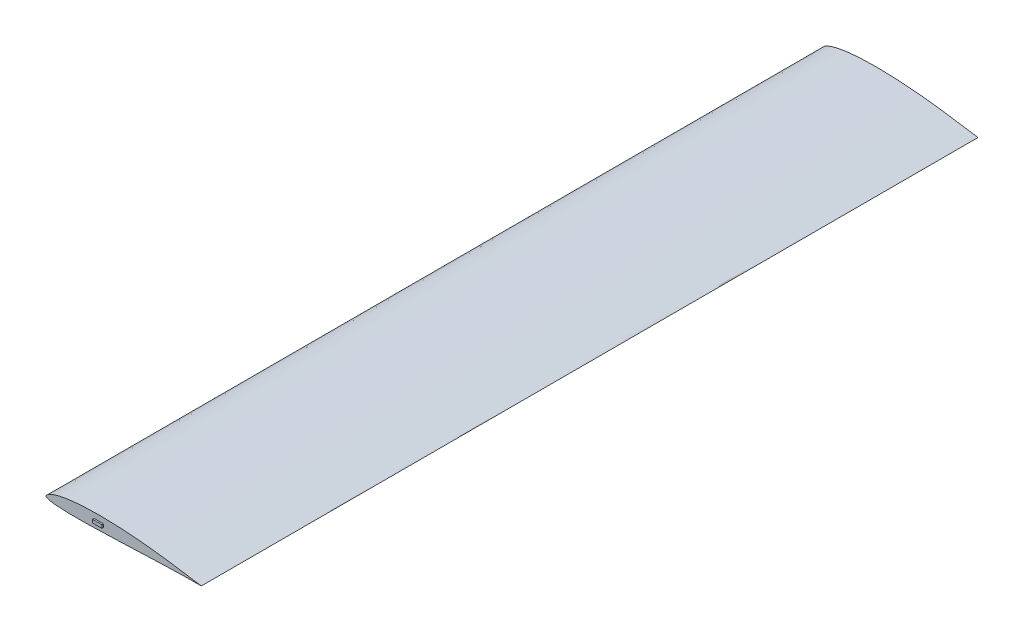
SolidWorks part; units mm, degrees
material "EPP"
ref_plane "Front Plane" through (0, 0, 0) normal (0, 0, 1) x (1, 0, 0)
ref_plane "Top Plane" through (0, 0, 0) normal (0, 1, 0) x (1, 0, 0)
ref_plane "Right Plane" through (0, 0, 0) normal (1, 0, 0) x (0, 0, -1)
curve "Curve1"
  spline degree 3 poles (49.6515, 0.009, 0) (50.0884, -0.0053, 0) (49.6522, 0.033, 0) (49.3011, 0.0832, 0) (48.4593, 0.1945, 0) (47.4415, 0.3499, 0) (46.1338, 0.5549, 0) (44.6155, 0.7993, 0) (42.8923, 1.0751, 0) (40.9958, 1.371, 0) (38.9477, 1.6747, 0) (36.7703, 1.9711, 0) (34.4838, 2.2498, 0) (32.109, 2.5048, 0) (29.6686, 2.7322, 0) (27.1889, 2.9318, 0) (24.6971, 3.0996, 0) (22.2188, 3.2252, 0) (19.7784, 3.3048, 0) (17.3996, 3.3388, 0) (15.1043, 3.321, 0) (12.9138, 3.2492, 0) (10.8475, 3.1296, 0) (8.9245, 2.9596, 0) (7.1613, 2.7404, 0) (5.5715, 2.4767, 0) (4.1671, 2.1739, 0) (2.9576, 1.8376, 0) (1.9505, 1.4773, 0) (1.1488, 1.103, 0) (0.5587, 0.7311, 0) (0.2281, 0.4366, 0) (0.09, 0.2394, 0) (0.0408, 0.1522, 0) (0.0104, 0.0738, 0) (-0.0015, 0.012, 0) (0.0009, -0.0367, 0) (0.0247, -0.0804, 0) (0.0694, -0.1305, 0) (0.1411, -0.1885, 0) (0.3144, -0.2962, 0) (0.7005, -0.4536, 0) (1.3781, -0.6282, 0) (2.3375, -0.7877, 0) (3.539, -0.9182, 0) (4.9742, -1.0154, 0) (6.6312, -1.0793, 0) (8.4956, -1.1107, 0) (10.5497, -1.112, 0) (12.7728, -1.0868, 0) (15.1414, -1.0389, 0) (17.6298, -0.9723, 0) (20.2103, -0.8906, 0) (22.8538, -0.7976, 0) (25.5303, -0.6969, 0) (28.2091, -0.5925, 0) (30.859, -0.4876, 0) (33.449, -0.3866, 0) (35.9478, -0.2924, 0) (38.325, -0.208, 0) (40.551, -0.1358, 0) (42.5964, -0.0785, 0) (44.4361, -0.0365, 0) (46.0378, -0.0091, 0) (47.399, 0.0043, 0) (48.4441, 0.0096, 0) (49.2972, 0.0042, 0) (49.6515, 0.009, 0) (50.0884, -0.0053, 0) (49.6522, 0.033, 0) knots -0.014204 -0.006419 -0.001632 0 0.001631 0.006435 0.014221 0.024766 0.037827 0.053149 0.070474 0.089536 0.110075 0.13186 0.154693 0.178371 0.20268 0.227364 0.252133 0.276728 0.300939 0.324527 0.347267 0.368992 0.389507 0.408628 0.426224 0.442179 0.456396 0.468805 0.479372 0.488086 0.494968 0.500034 0.501036 0.502094 0.502997 0.503513 0.503956 0.504409 0.504955 0.505943 0.50713 0.510998 0.518232 0.527846 0.539809 0.554056 0.57049 0.588974 0.609342 0.631393 0.654894 0.67959 0.705203 0.731447 0.75802 0.78462 0.810936 0.836657 0.861473 0.885081 0.907188 0.927507 0.945765 0.961712 0.975122 0.985796 0.993581 0.998368 1 1.001631 1.006435 1.014221 periodic
sketch "Sketch1" plane through (0, 0, 0) normal (0, 0, 1) x (1, 0, 0)
  spline S0 degree 3 poles (49.6515, 0.009) (50.0884, -0.0053) (49.6522, 0.033) (49.3011, 0.0832) (48.4593, 0.1945) (47.4415, 0.3499) (46.1338, 0.5549) (44.6155, 0.7993) (42.8923, 1.0751) (40.9958, 1.371) (38.9477, 1.6747) (36.7703, 1.9711) (34.4838, 2.2498) (32.109, 2.5048) (29.6686, 2.7322) (27.1889, 2.9318) (24.6971, 3.0996) (22.2188, 3.2252) (19.7784, 3.3048) (17.3996, 3.3388) (15.1043, 3.321) (12.9138, 3.2492) (10.8475, 3.1296) (8.9245, 2.9596) (7.1613, 2.7404) (5.5715, 2.4767) (4.1671, 2.1739) (2.9576, 1.8376) (1.9505, 1.4773) (1.1488, 1.103) (0.5587, 0.7311) (0.2281, 0.4366) (0.09, 0.2394) (0.0408, 0.1522) (0.0104, 0.0738) (-0.0015, 0.012) (0.0009, -0.0367) (0.0247, -0.0804) (0.0694, -0.1305) (0.1411, -0.1885) (0.3144, -0.2962) (0.7005, -0.4536) (1.3781, -0.6282) (2.3375, -0.7877) (3.539, -0.9182) (4.9742, -1.0154) (6.6312, -1.0793) (8.4956, -1.1107) (10.5497, -1.112) (12.7728, -1.0868) (15.1414, -1.0389) (17.6298, -0.9723) (20.2103, -0.8906) (22.8538, -0.7976) (25.5303, -0.6969) (28.2091, -0.5925) (30.859, -0.4876) (33.449, -0.3866) (35.9478, -0.2924) (38.325, -0.208) (40.551, -0.1358) (42.5964, -0.0785) (44.4361, -0.0365) (46.0378, -0.0091) (47.399, 0.0043) (48.4441, 0.0096) (49.2972, 0.0042) (49.6515, 0.009) (50.0884, -0.0053) (49.6522, 0.033) knots -0.014204 -0.006419 -0.001632 0 0.001631 0.006435 0.014221 0.024766 0.037827 0.053149 0.070474 0.089536 0.110075 0.13186 0.154693 0.178371 0.20268 0.227364 0.252133 0.276728 0.300939 0.324527 0.347267 0.368992 0.389507 0.408628 0.426224 0.442179 0.456396 0.468805 0.479372 0.488086 0.494968 0.500034 0.501036 0.502094 0.502997 0.503513 0.503956 0.504409 0.504955 0.505943 0.50713 0.510998 0.518232 0.527846 0.539809 0.554056 0.57049 0.588974 0.609342 0.631393 0.654894 0.67959 0.705203 0.731447 0.75802 0.78462 0.810936 0.836657 0.861473 0.885081 0.907188 0.927507 0.945765 0.961712 0.975122 0.985796 0.993581 0.998368 1 1.001631 1.006435 1.014221 only from (50, 0) to (50, 0) construction
  spline S1 degree 3 poles (49.6515, 0.009) (50.0884, -0.0053) (49.6522, 0.033) (49.3011, 0.0832) (48.4593, 0.1945) (47.4415, 0.3499) (46.1338, 0.5549) (44.6155, 0.7993) (42.8923, 1.0751) (40.9958, 1.371) (38.9477, 1.6747) (36.7703, 1.9711) (34.4838, 2.2498) (32.109, 2.5048) (29.6686, 2.7322) (27.1889, 2.9318) (24.6971, 3.0996) (22.2188, 3.2252) (19.7784, 3.3048) (17.3996, 3.3388) (15.1043, 3.321) (12.9138, 3.2492) (10.8475, 3.1296) (8.9245, 2.9596) (7.1613, 2.7404) (5.5715, 2.4767) (4.1671, 2.1739) (2.9576, 1.8376) (1.9505, 1.4773) (1.1488, 1.103) (0.5587, 0.7311) (0.2281, 0.4366) (0.09, 0.2394) (0.0408, 0.1522) (0.0104, 0.0738) (-0.0015, 0.012) (0.0009, -0.0367) (0.0247, -0.0804) (0.0694, -0.1305) (0.1411, -0.1885) (0.3144, -0.2962) (0.7005, -0.4536) (1.3781, -0.6282) (2.3375, -0.7877) (3.539, -0.9182) (4.9742, -1.0154) (6.6312, -1.0793) (8.4956, -1.1107) (10.5497, -1.112) (12.7728, -1.0868) (15.1414, -1.0389) (17.6298, -0.9723) (20.2103, -0.8906) (22.8538, -0.7976) (25.5303, -0.6969) (28.2091, -0.5925) (30.859, -0.4876) (33.449, -0.3866) (35.9478, -0.2924) (38.325, -0.208) (40.551, -0.1358) (42.5964, -0.0785) (44.4361, -0.0365) (46.0378, -0.0091) (47.399, 0.0043) (48.4441, 0.0096) (49.2972, 0.0042) (49.6515, 0.009) (50.0884, -0.0053) (49.6522, 0.033) knots -0.014204 -0.006419 -0.001632 0 0.001631 0.006435 0.014221 0.024766 0.037827 0.053149 0.070474 0.089536 0.110075 0.13186 0.154693 0.178371 0.20268 0.227364 0.252133 0.276728 0.300939 0.324527 0.347267 0.368992 0.389507 0.408628 0.426224 0.442179 0.456396 0.468805 0.479372 0.488086 0.494968 0.500034 0.501036 0.502094 0.502997 0.503513 0.503956 0.504409 0.504955 0.505943 0.50713 0.510998 0.518232 0.527846 0.539809 0.554056 0.57049 0.588974 0.609342 0.631393 0.654894 0.67959 0.705203 0.731447 0.75802 0.78462 0.810936 0.836657 0.861473 0.885081 0.907188 0.927507 0.945765 0.961712 0.975122 0.985796 0.993581 0.998368 1 1.001631 1.006435 1.014221 only from (50, 0) to (50, 0)
extrude "Boss-Extrude1" add sketch "Sketch1" along normal blind 250
sketch "Sketch2" plane through (0, 0, 250) normal (0, 0, 1) x (1, 0, 0)
  line L0 (0, 0) -> (50, 0) construction
  line L1 (15.473, 1.5494) -> (18.473, 1.5494)
  line L2 (15.473, 1.5494) -> (15.473, 0.5494)
  line L3 (15.473, 0.5494) -> (18.473, 0.5494)
  line L4 (18.473, 1.5494) -> (18.473, 0.5494)
  spline S0 degree 3 poles (49.6515, 0.009) (50.0884, -0.0053) (49.6522, 0.033) (49.3011, 0.0832) (48.4593, 0.1945) (47.4415, 0.3499) (46.1338, 0.5549) (44.6155, 0.7993) (42.8923, 1.0751) (40.9958, 1.371) (38.9477, 1.6747) (36.7703, 1.9711) (34.4838, 2.2498) (32.109, 2.5048) (29.6686, 2.7322) (27.1889, 2.9318) (24.6971, 3.0996) (22.2188, 3.2252) (19.7784, 3.3048) (17.3996, 3.3388) (15.1043, 3.321) (12.9138, 3.2492) (10.8475, 3.1296) (8.9245, 2.9596) (7.1613, 2.7404) (5.5715, 2.4767) (4.1671, 2.1739) (2.9576, 1.8376) (1.9505, 1.4773) (1.1488, 1.103) (0.5587, 0.7311) (0.2281, 0.4366) (0.09, 0.2394) (0.0408, 0.1522) (0.0104, 0.0738) (-0.0015, 0.012) (0.0009, -0.0367) (0.0247, -0.0804) (0.0694, -0.1305) (0.1411, -0.1885) (0.3144, -0.2962) (0.7005, -0.4536) (1.3781, -0.6282) (2.3375, -0.7877) (3.539, -0.9182) (4.9742, -1.0154) (6.6312, -1.0793) (8.4956, -1.1107) (10.5497, -1.112) (12.7728, -1.0868) (15.1414, -1.0389) (17.6298, -0.9723) (20.2103, -0.8906) (22.8538, -0.7976) (25.5303, -0.6969) (28.2091, -0.5925) (30.859, -0.4876) (33.449, -0.3866) (35.9478, -0.2924) (38.325, -0.208) (40.551, -0.1358) (42.5964, -0.0785) (44.4361, -0.0365) (46.0378, -0.0091) (47.399, 0.0043) (48.4441, 0.0096) (49.2972, 0.0042) (49.6515, 0.009) (50.0884, -0.0053) (49.6522, 0.033) knots -0.014204 -0.006419 -0.001632 0 0.001631 0.006435 0.014221 0.024766 0.037827 0.053149 0.070474 0.089536 0.110075 0.13186 0.154693 0.178371 0.20268 0.227364 0.252133 0.276728 0.300939 0.324527 0.347267 0.368992 0.389507 0.408628 0.426224 0.442179 0.456396 0.468805 0.479372 0.488086 0.494968 0.500034 0.501036 0.502094 0.502997 0.503513 0.503956 0.504409 0.504955 0.505943 0.50713 0.510998 0.518232 0.527846 0.539809 0.554056 0.57049 0.588974 0.609342 0.631393 0.654894 0.67959 0.705203 0.731447 0.75802 0.78462 0.810936 0.836657 0.861473 0.885081 0.907188 0.927507 0.945765 0.961712 0.975122 0.985796 0.993581 0.998368 1 1.001631 1.006435 1.014221 only from (50, 0) to (50, 0) construction
  dimension "D1" = 3
  dimension "D2" = 1
  dimension "D3" = 1.5494
  dimension "D4" = 31.527
extrude "Boss-Extrude2" add sketch "Sketch2" along normal blind 0.5
